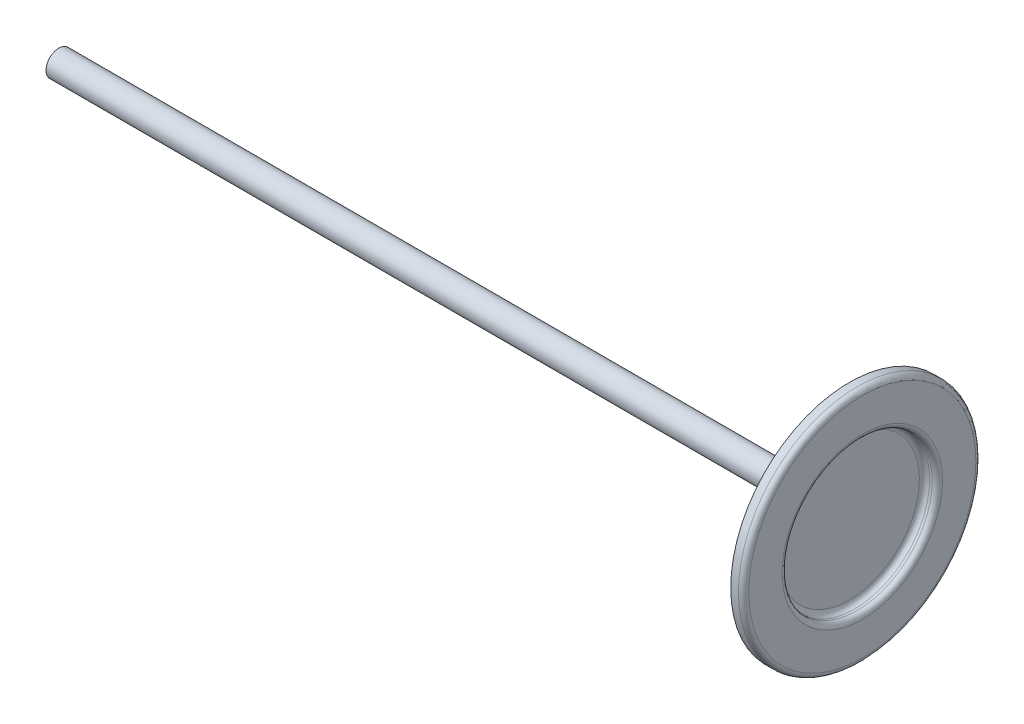
SolidWorks part; units mm, degrees
ref_plane "Front Plane" through (0, 0, 0) normal (1, 0, 0) x (0, 1, 0)
ref_plane "Top Plane" through (0, 0, 0) normal (0, 0, 1) x (0, 1, 0)
ref_plane "Right Plane" through (0, 0, 0) normal (0, 1, 0) x (-1, 0, 0)
sketch "Sketch1" plane through (0, 0, 0) normal (1, 0, 0) x (0, 1, 0)
  circle A0 centre (0, 0) radius 6.85
  dimension "D1" = 13.7
extrude "Boss-Extrude1" add sketch "Sketch1" along normal blind 1.6
sketch "Sketch2" plane through (1.6, 0, 0) normal (1, 0, 0) x (0, 1, 0)
  circle A0 centre (0, 0) radius 5.85
  circle A1 centre (0, 0) radius 9.25
  circle A2 centre (0, 0) radius 6.85 construction
  dimension "D1" = 1
  dimension "D2" = 2.4
extrude "Boss-Extrude2" add sketch "Sketch2" along normal blind 1
fillet "Fillet1" radius 0.4 2 edges at (1.6, 0, -5.85) (2.6, 0, -5.85)
fillet "Fillet2" radius 0.4 1 edges at (2.6, 0, -9.25)
sketch "Sketch3" plane through (0, 0, 0) normal (-1, 0, 0) x (0, -1, 0)
  circle A0 centre (0, 0) radius 1
  dimension "D1" = 2
extrude "Boss-Extrude3" add sketch "Sketch3" along normal blind 60
fillet "Fillet3" radius 0.4 1 edges at (0, 0, -1)
